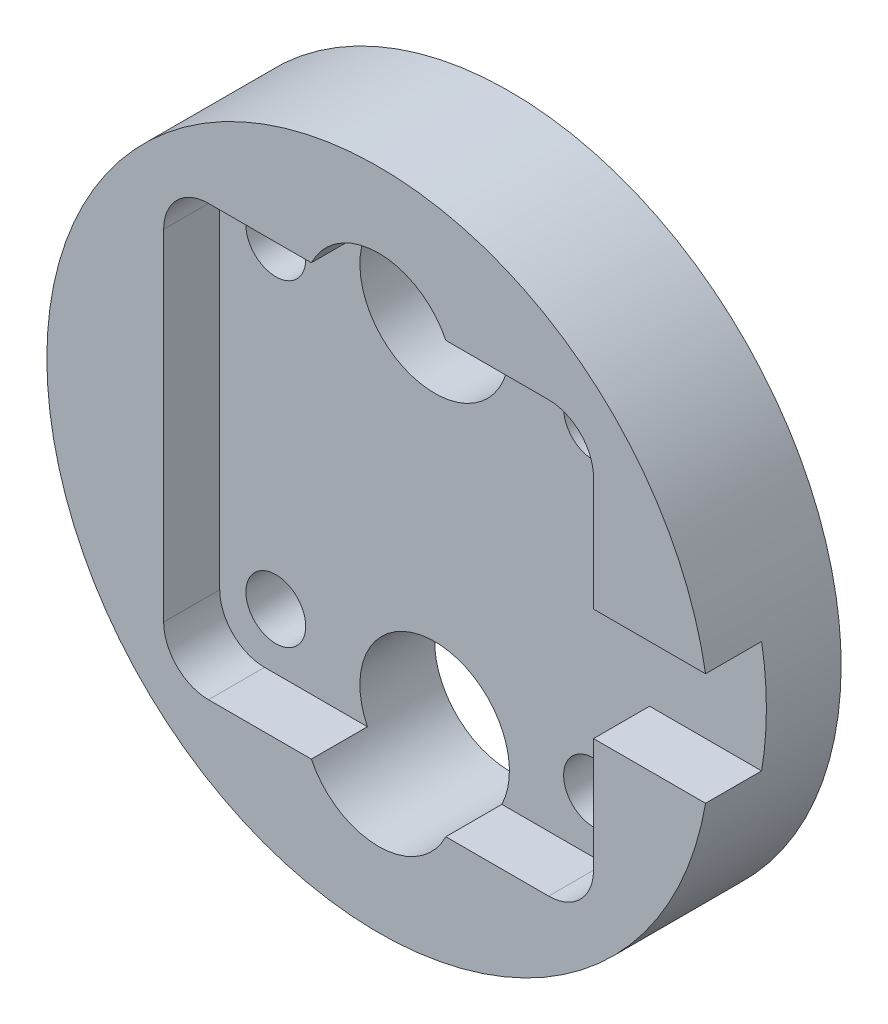
SolidWorks part; units mm, degrees
ref_plane "Front Plane" through (0, 0, 0) normal (1, 0, 0) x (0, 1, 0)
ref_plane "Top Plane" through (0, 0, 0) normal (0, 0, 1) x (0, 1, 0)
ref_plane "Right Plane" through (0, 0, 0) normal (0, 1, 0) x (-1, 0, 0)
sketch "Sketch1" plane through (0, 0, 0) normal (0, 0, 1) x (0, 1, 0)
  line L1 (-11.5, -11.5) -> (11.5, -11.5)
  line L2 (-11.5, -11.5) -> (-11.5, 11.5)
  line L3 (-11.5, 11.5) -> (11.5, 11.5)
  line L4 (11.5, -11.5) -> (11.5, 11.5)
  line L5 (-11.5, -11.5) -> (11.5, 11.5) construction
  line L6 (-11.5, 11.5) -> (11.5, -11.5) construction
  circle A0 centre (0, 0) radius 17.75
  circle A1 centre (-8.5, 8.5) radius 1.6
  circle A2 centre (8.5, 8.5) radius 1.6
  circle A3 centre (8.5, -8.5) radius 1.6
  circle A4 centre (-8.5, -8.5) radius 1.6
  circle A5 centre (9.75, 0) radius 4
  circle A6 centre (0, 0) radius 13.75 construction
  circle A7 centre (-9.75, 0) radius 4
  point P0 (0, 0)
  point P20 (0, 0)
  dimension "D1" = 35.5
  dimension "D3" = 3.2
  dimension "D5" = 17
  dimension "D6" = 27.5
  dimension "D7" = 8
  dimension "D2" = 23
  dimension "D4" = 4
extrude "Boss-Extrude1" add sketch "Sketch1" along normal blind 7 contours L1 L4 L3 L2 A4 A3 A2 A1 | A4 | A3 | A1 | A2 | A0 L4 L1 L2 L3 region at (0, 0, 0) region at (0, -17.248, 0) region at (-8.5, -8.5, 0) region at (-8.5, 8.5, 0) region at (8.5, 8.5, 0) region at (8.5, -8.5, 0)
extrude "Cut-Extrude1" cut sketch "Sketch1<3>" against normal blind 3 from surface contours L1 L4 L3 L2 A4 A3 A2 A1 | A1 | A2 | A4 | A3 region at (0, 0, 0) region at (-8.5, -8.5, 0) region at (-8.5, 8.5, 0) region at (8.5, 8.5, 0) region at (8.5, -8.5, 0) starting at face at (4, -9.75, 7)
sketch "Sketch1<3>" plane through (0, 0, 0) normal (0, 0, 1) x (0, 1, 0) same geometry as "Sketch1"
extrude "Cut-Extrude3" cut sketch "Sketch1<4>" along normal through all contours A4 | A3 | A2 | A1 region at (-8.5, -8.5, 0) region at (-8.5, 8.5, 0) region at (8.5, 8.5, 0) region at (8.5, -8.5, 0)
sketch "Sketch1<4>" plane through (0, 0, 0) normal (0, 0, 1) x (0, 1, 0) same geometry as "Sketch1"
sketch "Sketch2" plane through (0, 0, 7) normal (0, 0, 1) x (1, 0, 0)
  line L0 (11.5, 3) -> (17.4946, 3)
  line L1 (11.5, 11.5) -> (11.5, -11.5) construction
  line L2 (11.5, -3) -> (17.4946, -3)
  line L3 (11.5, 3) -> (11.5, -3)
  circle A0 centre (0, 0) radius 17.75 construction
  arc A1 (17.4946, 3) -> (17.4946, -3) centre (0, 0) cw
  dimension "D1" = 6
extrude "Cut-Extrude4" cut sketch "Sketch2" against normal up to surface (3 mm away) up to face at (-6.9, -8.5, 4)
fillet "Fillet1" radius 2.4 4 edges at (-11.5, -11.5, 5.5) (11.5, -11.5, 5.5) (11.5, 11.5, 5.5) (-11.5, 11.5, 5.5)
equation "\"AS5600Height\"= 3"
equation "\"D1@Cut-Extrude1\"=\"AS5600Height\""
